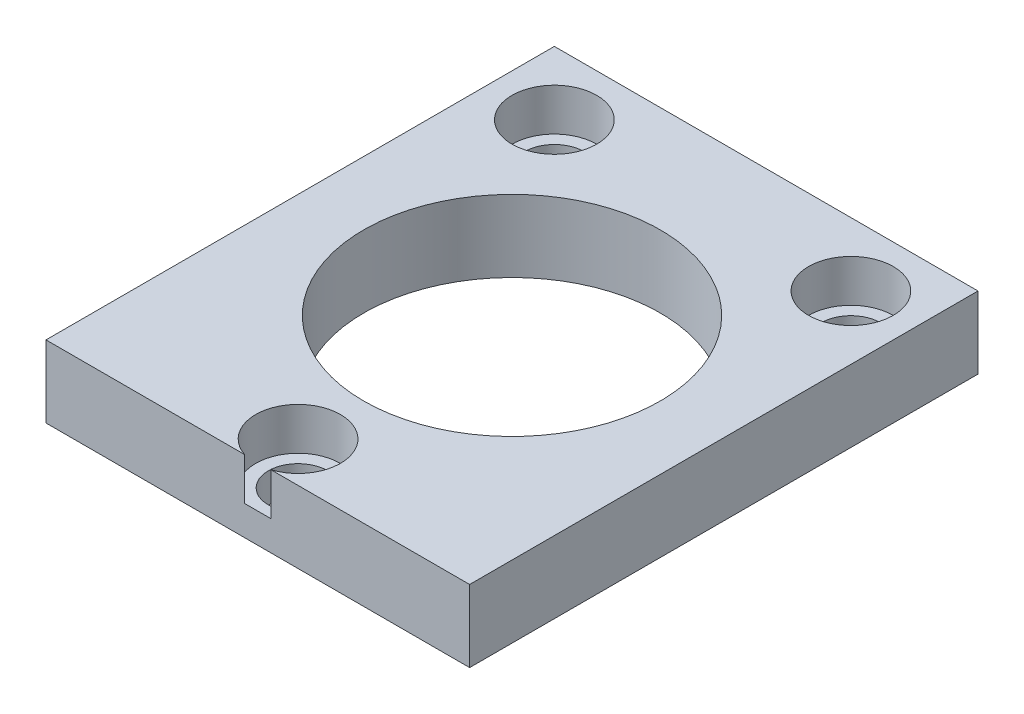
SolidWorks part; units mm, degrees
ref_plane "前视基准面" through (0, 0, 0) normal (0, 0, 1) x (1, 0, 0)
ref_plane "上视基准面" through (0, 0, 0) normal (0, 1, 0) x (1, 0, 0)
ref_plane "右视基准面" through (0, 0, 0) normal (1, 0, 0) x (0, 0, -1)
other "Configuration Table"
sketch "草图1" plane through (0, 0, 0) normal (0, 1, 0) x (1, 0, 0)
  line L7 (-5, -6) -> (5, -6)
  line L8 (-5, -6) -> (-5, 6)
  line L9 (-5, 6) -> (5, 6)
  line L10 (5, -6) -> (5, 6)
  circle A0 centre (0, 0) radius 3.5
  point P0 (0, 0)
  point P5 (0, 0)
  dimension "D1" = 7
  dimension "D2" = 10
  dimension "D3" = 6
  dimension "D4" = 6
  dimension "D5" = 5
extrude "凸台-拉伸1" add sketch "草图1" along normal blind 1.7 contours L9 L10 L7 L8 | A0
sketch "草图2" plane through (0, 0, 0) normal (0, -1, 0) x (1, 0, 0)
  circle A0 centre (0, 5.05) radius 1
  circle A1 centre (0, 5.05) radius 0.7
  circle A5 centre (3.5, -4.5) radius 1
  circle A6 centre (3.5, -4.5) radius 0.7
  circle A7 centre (-3.5, -4.5) radius 1
  circle A8 centre (-3.5, -4.5) radius 0.7
  point P9 (0, 0)
  point P10 (0, 0)
  point P11 (0, 0)
  dimension "D1" = 2
  dimension "D2" = 1.4
extrude "切除-拉伸1" cut sketch "草图2" against normal through all contours A6 | A8 | A1
extrude "切除-拉伸2" cut sketch "草图2<3>" along normal blind 1 from surface contours A0 | A5 | A7 starting at face at (3.5, 1.7, -5.2)
sketch "草图2<3>" plane through (0, 0, 0) normal (0, -1, 0) x (1, 0, 0) same geometry as "草图2"
